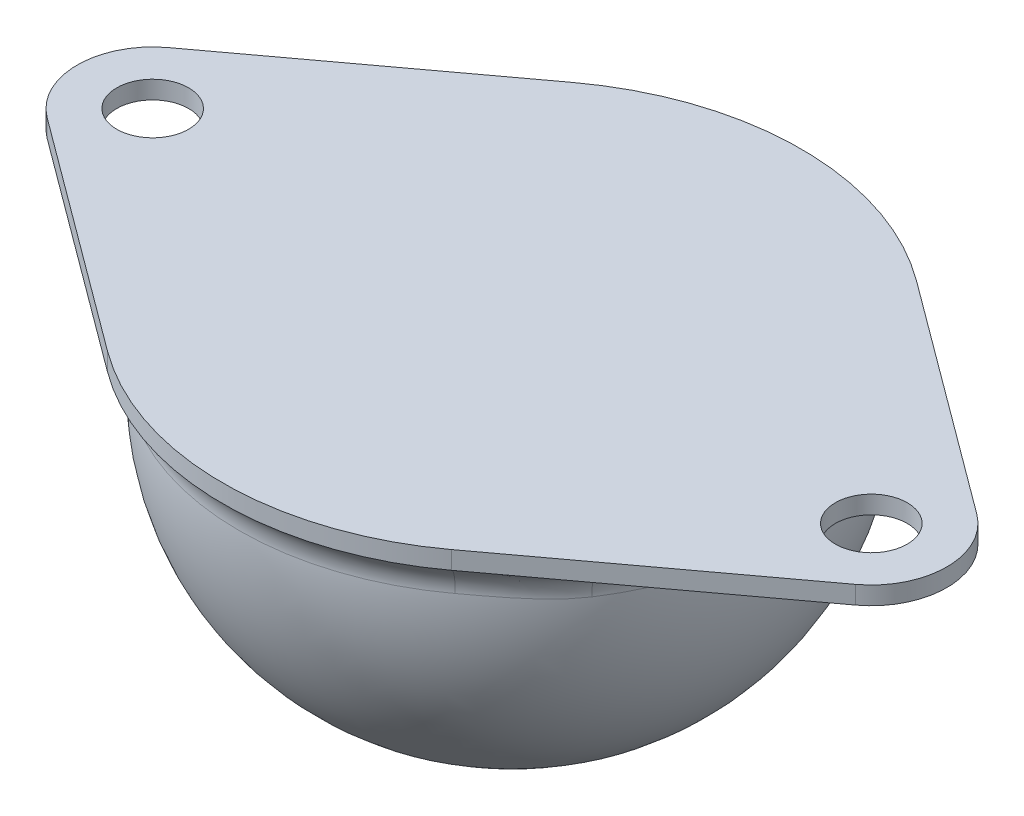
SolidWorks part; units mm, degrees
material "Простая углеродистая сталь"
ref_plane "Front" through (0, 0, 0) normal (0, 0, 1) x (1, 0, 0)
ref_plane "Top" through (0, 0, 0) normal (0, 1, 0) x (1, 0, 0)
ref_plane "Right" through (0, 0, 0) normal (1, 0, 0) x (0, 0, -1)
sketch "Эскиз2" plane through (0, 0, 0) normal (0, 0, 1) x (1, 0, 0)
  line L0 (0, 0) -> (0, -7)
  line L5 (0, -7) -> (0, 13.5)
  line L6 (0, 13.5) -> (50, 13.5)
  line L7 (50, 13.5) -> (50, 12.5)
  line L8 (50, 12.5) -> (0, 12.5)
  line L10 (0, -3) -> (7.4, -3)
  arc A0 (6.6002, -3) -> (0, 7.25) centre (0, 0) ccw
  circle A2 centre (0, 12.5) radius 15 construction
  arc A3 (7.4, -3) -> (15, 12.5) centre (0.1851, 10.1509) ccw
  dimension "D5" = 30
  dimension "D8" = 14.5
  dimension "D9" = 15
  dimension "D1" = 7
  dimension "D2" = 20.5
  dimension "D3" = 1
  dimension "D4" = 50
  dimension "D6" = 4
  dimension "D7" = 7.4
revolve "Повернуть3" add sketch "Эскиз2" angle 360 about L0 region at (8.3685, 7.1031, 0) region at (25, 13, 0)
sketch "Эскиз3" plane through (0, 13.5, 0) normal (0, 1, 0) x (1, 0, 0)
  line L0 (0, 0) -> (-24.2, 0) construction
  line L1 (0, 0) -> (0, 16.1) construction
  line L2 (-22.499, 3.3756) -> (-9.5795, 12.94)
  line L3 (-22.499, -3.3756) -> (-9.5795, -12.94)
  line L4 (22.499, -3.3756) -> (9.5795, -12.94)
  line L5 (22.499, 3.3756) -> (9.5795, 12.94)
  circle A0 centre (0, 0) radius 16.1
  circle A2 centre (0, 0) radius 20 construction
  circle A3 centre (-20, 0) radius 2
  circle A5 centre (-20, 0) radius 4.2
  circle A6 centre (20, 0) radius 4.2
  circle A7 centre (20, 0) radius 2
  circle A8 centre (0, 0) radius 73.0036
  circle M5 centre (0, 0) radius 50
  dimension "D3" = 4
  dimension "D4" = 40
  dimension "D1" = 24.2
  dimension "D2" = 16.1
extrude "Вырез-Вытянуть1" cut sketch "Эскиз3" against normal through all both and the other way through all contours L5 A6 L4 A0 L3 A5 L2 M5 | A8 M5 | A3 | A7 region at (-20, 13.5, 0) region at (20, 13.5, 0) region at (-70.9388, 13.5, 0) region at (-48.5858, 13.5, 0)
fillet "Скругление1" radius 2 1 edges at (-15, 12.5, 0)
sketch3d "3DSketch1"
  line L0 (0, 0, 0) -> (10, 0, 0) construction
  line L2 (0, 0, 0) -> (0, 0, -10) construction
  line L3 (0, 0, 0) -> (0, 10, 0) construction
